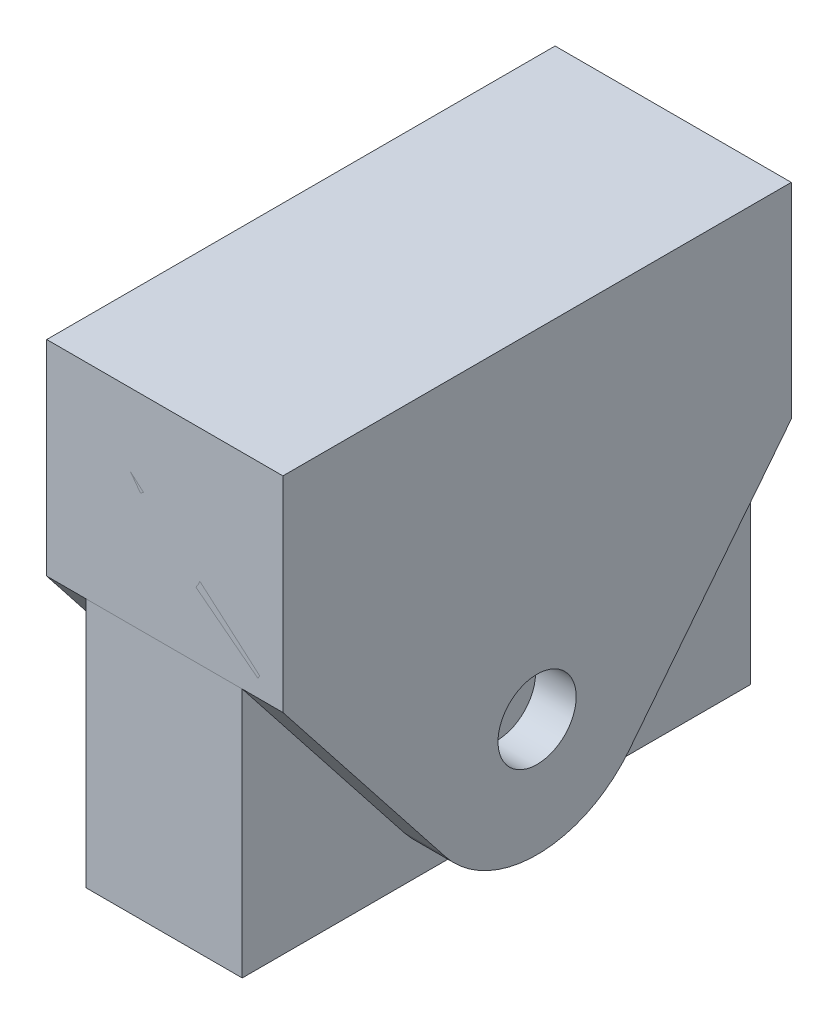
SolidWorks part; units mm, degrees
ref_plane "Front Plane" through (0, 0, 0) normal (0, 0, 1) x (1, 0, 0)
ref_plane "Top Plane" through (0, 0, 0) normal (0, 1, 0) x (1, 0, 0)
ref_plane "Right Plane" through (0, 0, 0) normal (1, 0, 0) x (0, 0, -1)
sketch "Sketch1" plane through (0, 0, 0) normal (0, 0, 1) x (1, 0, 0)
  line L0 (0, 0) -> (0, 5.0831)
  line L1 (3.175, 5.0831) -> (3.175, 0)
  line L2 (3.175, 0) -> (0, 0)
  arc A0 (0, 5.0831) -> (3.175, 5.0831) centre (1.5875, 6.858) cw
  circle A1 centre (1.5875, 6.858) radius 0.7938
  dimension "D2" = 2.3813
  dimension "D4" = 1.5875
  dimension "D1" = 6.858
  dimension "D3" = 3.175
sketch "Sketch2" plane through (0, 0, 0) normal (1, 0, 0) x (0, 0, -1)
  line L0 (-1.8701, 0.9071) -> (-5.1594, 5.08)
  line L1 (-5.1594, 5.08) -> (-5.1594, 9.2392)
  line L2 (-5.1594, 9.2392) -> (5.1594, 9.2392)
  line L3 (5.1594, 9.2392) -> (5.1594, 5.08)
  line L4 (5.1594, 5.08) -> (1.8701, 0.9071)
  arc A0 (1.8701, 0.9071) -> (-1.8701, 0.9071) centre (0, 2.3813) cw
  circle A1 centre (0, 2.3813) radius 0.7938
  point P3 (0, 0)
  point P11 (-5.1594, 6.858)
  dimension "D1" = 2.3813
  dimension "D6" = 1.5875
  dimension "D2" = 5.1594
  dimension "D3" = 5.08
  dimension "D4" = 2.3813
  dimension "D5" = 6.858
extrude "Boss-Extrude1" add sketch "Sketch1" along normal blind 5.1594 and the other way blind 5.1594
extrude "Boss-Extrude2" add sketch "Sketch2" along normal blind 4.0005 and the other way blind 0.7937 separate body
equation "\"D4@Sketch2\"= \"D2@Sketch1\""
equation "\"D5@Sketch2\"= \"D1@Sketch1\""
